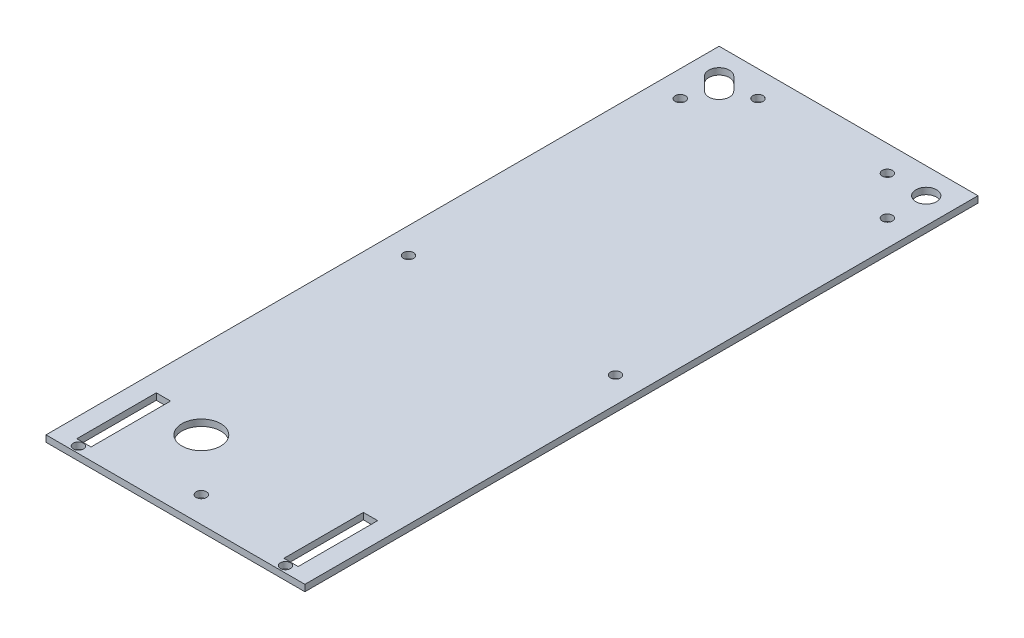
SolidWorks part; units mm, degrees
ref_plane "Front Plane" through (0, 0, 0) normal (0, 0, 1) x (1, 0, 0)
ref_plane "Top Plane" through (0, 0, 0) normal (0, 1, 0) x (1, 0, 0)
ref_plane "Right Plane" through (0, 0, 0) normal (1, 0, 0) x (0, 0, -1)
sketch "Sketch1" plane through (0, 0, 0) normal (0, 1, 0) x (1, 0, 0)
  line L1 (63.5, -165.1) -> (-63.5, -165.1)
  line L2 (63.5, -165.1) -> (63.5, 165.1)
  line L3 (63.5, 165.1) -> (-63.5, 165.1)
  line L4 (-63.5, -165.1) -> (-63.5, 165.1)
  line L5 (63.5, -165.1) -> (-63.5, 165.1) construction
  line L6 (63.5, 165.1) -> (-63.5, -165.1) construction
  point P0 (0, 0)
  dimension "D1" = 330.2
  dimension "D2" = 127
extrude "Boss-Extrude1" add sketch "Sketch1" along normal blind 3.175
sketch "Sketch2" plane through (0, 3.175, 0) normal (0, 1, 0) x (1, 0, 0)
  line L0 (-63.5, 165.1) -> (-63.5, -165.1) construction
  line L1 (63.5, 165.1) -> (-63.5, 165.1) construction
  line L2 (0, 165.1) -> (0, 0) construction
  line L3 (0, 0) -> (-63.5, 0) construction
  line L4 (-63.5, -165.1) -> (63.5, -165.1) construction
  line L8 (-54.3921, 148.8079) -> (-48.0421, 142.4579)
  line L9 (-47.2079, 155.9921) -> (-40.8579, 149.6421)
  circle A0 centre (-50.8, 152.4) radius 2.5
  circle A1 centre (-44.45, 146.05) radius 2.5
  circle A3 centre (50.8, 152.4) radius 2.5
  circle A6 centre (50.8, 152.4) radius 2.5
  arc A36 (-48.0421, 142.4579) -> (-40.8579, 149.6421) centre (-44.45, 146.05) ccw
  arc A37 (-47.2079, 155.9921) -> (-54.3921, 148.8079) centre (-50.8, 152.4) ccw
  circle A38 centre (50.8, 152.4) radius 5.08
  circle A39 centre (-31.75, 152.4) radius 2.5
  circle A40 centre (31.75, 152.4) radius 2.5
  circle A41 centre (-50.8, 133.35) radius 2.5
  circle A42 centre (50.8, 133.35) radius 2.5
  circle A47 centre (-50.8, -161.925) radius 2.5
  circle A48 centre (50.8, -161.925) radius 2.5
  circle A51 centre (-50.8, 0) radius 2.5
  circle A53 centre (50.8, 0) radius 2.5
  circle A54 centre (0, -152.4) radius 2.5
  dimension "D1" = 5
  dimension "D15" = 10.16
  dimension "D6" = 31.75
  dimension "D2" = 12.7
  dimension "D3" = 12.7
  dimension "D4" = 19.05
  dimension "D5" = 19.05
  dimension "D7" = 12.7
  dimension "D8" = 12.7
  dimension "D9" = 31.75
  dimension "D10" = 12.7
  dimension "D11" = 3.175
  dimension "D12" = 12.7
extrude "Cut-Extrude1" cut sketch "Sketch2" against normal blind 25.4 contours A3 | A0 | A1 | L9 A37 L8 A36 A1 A0 | A38 A3 | A39 | A40 | A41 | A42 | A47 | A48 | A51 | A53 | A54
sketch "Sketch3" plane through (0, 3.175, 0) normal (0, 1, 0) x (1, 0, 0)
  line L0 (-63.5, -165.1) -> (63.5, -165.1) construction
  line L1 (63.5, -139.7) -> (-63.5, -139.7) construction
  line L2 (-63.5, 165.1) -> (-63.5, -165.1) construction
  line L3 (63.5, -165.1) -> (63.5, 165.1) construction
  line L4 (63.5, 165.1) -> (-63.5, 165.1) construction
  line L5 (-54.3, -159.2) -> (-47.3, -152.2) construction
  line L6 (-54.3, -127.2) -> (-47.3, -127.2) construction
  line L7 (-54.3, -127.2) -> (-54.3, -120.2)
  line L8 (-54.3, -120.2) -> (-47.3, -120.2)
  line L9 (-47.3, -127.2) -> (-47.3, -120.2)
  line L10 (-54.3, -127.2) -> (-47.3, -120.2) construction
  line L11 (-54.3, -120.2) -> (-47.3, -127.2) construction
  line L12 (-54.3, -152.2) -> (-47.3, -159.2) construction
  line L13 (-47.3, -152.2) -> (-47.3, -159.2)
  line L14 (-54.3, -159.2) -> (-47.3, -159.2)
  line L15 (-54.3, -152.2) -> (-54.3, -159.2)
  line L16 (-54.3, -152.2) -> (-47.3, -152.2) construction
  line L17 (-47.3, -152.2) -> (-47.3, -127.2)
  line L18 (-54.3, -120.2) -> (-47.3, -120.2)
  line L20 (-54.3, -159.2) -> (-47.3, -159.2)
  line L22 (-54.3, -127.2) -> (-54.3, -152.2)
  line L23 (0, -139.7) -> (0, -165.1) construction
  line L24 (54.3, -152.2) -> (47.3, -152.2) construction
  line L25 (54.3, -152.2) -> (47.3, -159.2) construction
  line L26 (54.3, -120.2) -> (47.3, -127.2) construction
  line L27 (54.3, -127.2) -> (47.3, -120.2) construction
  line L28 (54.3, -127.2) -> (47.3, -127.2) construction
  line L29 (54.3, -159.2) -> (47.3, -152.2) construction
  line L30 (54.3, -127.2) -> (54.3, -152.2)
  line L31 (54.3, -159.2) -> (47.3, -159.2)
  line L32 (54.3, -120.2) -> (47.3, -120.2)
  line L33 (47.3, -152.2) -> (47.3, -127.2)
  line L34 (54.3, -152.2) -> (54.3, -159.2)
  line L35 (54.3, -159.2) -> (47.3, -159.2)
  line L36 (47.3, -152.2) -> (47.3, -159.2)
  line L37 (47.3, -127.2) -> (47.3, -120.2)
  line L38 (54.3, -120.2) -> (47.3, -120.2)
  line L39 (54.3, -127.2) -> (54.3, -120.2)
  circle A0 centre (-25.4, -127) radius 9.525
  point P12 (-50.8, -123.7)
  point P21 (-50.8, -155.7)
  point P32 (50.8, -155.7)
  point P33 (50.8, -123.7)
  circle M17 centre (-50.8, -161.925) radius 2.5
  dimension "D1" = 19.05
  dimension "D2" = 38.1
  dimension "D3" = 38.1
  dimension "D4" = 304.8
  dimension "D5" = 7
  dimension "D6" = 16
  dimension "D7" = 12.7
extrude "Cut-Extrude2" cut sketch "Sketch3" against normal blind 25.4 contours L7 L22 L15 L14 L13 L17 L9 L8 M17 | A0 | L30 L39 L32 L37 L33 L36 L31 L34 region at (-50.8, 3.175, 139.7) region at (50.8, 3.175, 139.7) region at (-25.4, 3.175, 127)
